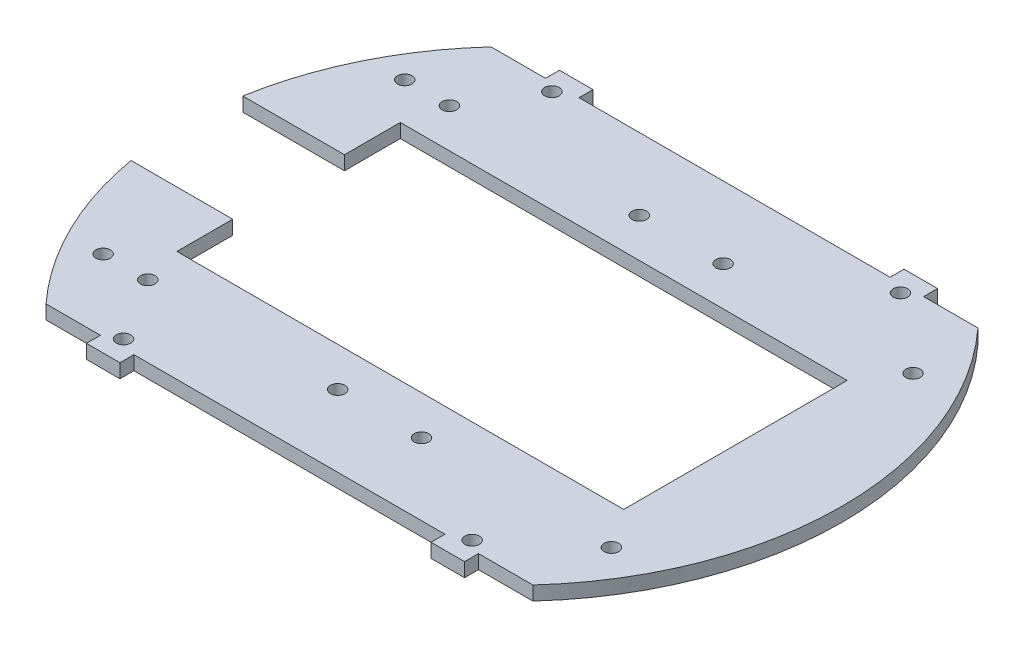
SolidWorks part; units mm, degrees
material "Acrylic (Medium-high impact)"
ref_plane "Front Plane" through (0, 0, 0) normal (0, 0, 1) x (1, 0, 0)
ref_plane "Top Plane" through (0, 0, 0) normal (0, 1, 0) x (1, 0, 0)
ref_plane "Right Plane" through (0, 0, 0) normal (1, 0, 0) x (0, 0, -1)
sketch "Sketch1" plane through (0, 0, 0) normal (0, 1, 0) x (1, 0, 0)
  line L0 (-73.9169, 12.7) -> (-73.9169, -12.7)
  line L1 (-35.3642, -50.6035) -> (-35.3642, -53.7785)
  line L2 (-55.356, -50.6035) -> (-42.9842, -50.6035)
  line L3 (-55.356, 50.6035) -> (-42.9842, 50.6035)
  line L4 (-48.5169, -34.29) -> (-48.5169, 34.29) construction
  line L5 (-48.5169, 34.29) -> (-5.3369, 34.29) construction
  line L6 (-5.3369, 34.29) -> (-5.3369, -34.29) construction
  line L7 (-5.3369, -34.29) -> (-48.5169, -34.29) construction
  line L8 (-73.9169, 0) -> (-48.5169, 0) construction
  line L9 (0, 50.6035) -> (0, -51.6195) construction
  line L10 (-73.9169, 12.7) -> (-73.9169, -12.7) construction
  line L11 (-50.8, 25.4) -> (50.8, 25.4)
  line L12 (-50.8, 25.4) -> (-50.8, -25.4)
  line L13 (-50.8, -25.4) -> (50.8, -25.4)
  line L14 (50.8, 25.4) -> (50.8, -25.4)
  line L15 (0, 0) -> (0, 25.4) construction
  line L16 (0, 0) -> (-50.8, 0) construction
  line L17 (13.7131, 34.29) -> (13.7131, -34.29) construction
  line L18 (13.7131, -34.29) -> (56.8931, -34.29) construction
  line L19 (56.8931, -34.29) -> (56.8931, 34.29) construction
  line L20 (56.8931, 34.29) -> (13.7131, 34.29) construction
  line L21 (39.6269, 48.6985) -> (39.6269, 50.6035) construction
  line L22 (39.6269, -48.6985) -> (39.6269, -50.6035) construction
  line L23 (-39.6269, -48.6985) -> (-39.6269, -50.6035) construction
  line L24 (-39.6269, 48.6985) -> (-39.6269, 50.6035) construction
  line L25 (39.6269, 48.6985) -> (41.2779, 48.6985) construction
  line L26 (39.6269, -48.6985) -> (41.2779, -48.6985) construction
  line L27 (-35.3642, -50.6035) -> (35.3642, -50.6035)
  line L28 (35.3642, -50.6035) -> (35.3642, -53.7785)
  line L29 (35.3642, -53.7785) -> (42.9842, -53.7785)
  line L30 (42.9842, -50.6035) -> (42.9842, -53.7785)
  line L31 (-35.3642, -53.7785) -> (-42.9842, -53.7785)
  line L32 (-42.9842, -50.6035) -> (-42.9842, -53.7785)
  line L33 (42.9842, 50.6035) -> (42.9842, 53.7785)
  line L34 (35.3642, 53.7785) -> (42.9842, 53.7785)
  line L35 (35.3642, 50.6035) -> (35.3642, 53.7785)
  line L36 (-35.3642, 50.6035) -> (-35.3642, 53.7785)
  line L37 (-35.3642, 53.7785) -> (-42.9842, 53.7785)
  line L38 (-42.9842, 50.6035) -> (-42.9842, 53.7785)
  line L39 (42.9842, -50.6035) -> (55.356, -50.6035)
  line L40 (42.9842, 50.6035) -> (55.356, 50.6035)
  line L41 (-35.3642, 50.6035) -> (35.3642, 50.6035)
  arc A0 (-73.9169, -12.7) -> (-55.356, -50.6035) centre (0, 0) ccw
  circle A1 centre (13.7131, 34.29) radius 1.651
  arc A2 (-55.356, 50.6035) -> (-73.9169, 12.7) centre (0, 0) ccw
  arc A3 (55.356, -50.6035) -> (55.356, 50.6035) centre (0, 0) ccw
  circle A4 centre (-58.6769, -34.29) radius 1.651
  circle A5 centre (-58.6769, 34.29) radius 1.651
  circle A6 centre (-39.6269, 48.6985) radius 1.651
  circle A7 centre (39.6269, 48.6985) radius 1.651
  circle A8 centre (-39.6269, -48.6985) radius 1.651
  circle A9 centre (39.6269, -48.6985) radius 1.651
  circle A10 centre (56.8931, 34.29) radius 1.651
  circle A11 centre (-58.6769, 34.29) radius 1.651 construction
  circle A12 centre (-48.5169, 34.29) radius 1.651
  circle A13 centre (-5.3369, 34.29) radius 1.651
  circle A14 centre (-5.3369, -34.29) radius 1.651
  circle A15 centre (-48.5169, -34.29) radius 1.651
  circle A16 centre (13.7131, -34.29) radius 1.651
  circle A17 centre (56.8931, -34.29) radius 1.651
  dimension "D3" = 3.302
  dimension "D1" = 43.18
  dimension "D2" = 68.58
  dimension "D4" = 25.4
  dimension "D5" = 101.6
  dimension "D6" = 50.8
  dimension "D7" = 19.05
  dimension "D10" = 19.05
extrude "Boss-Extrude1" add sketch "Sketch1" along normal blind 3.175
sketch "Sketch3" plane through (0, 3.175, 0) normal (0, 1, 0) x (1, 0, 0)
  line L0 (-50.8, 25.4) -> (-50.8, -25.4) construction
  line L1 (-73.9169, 12.7) -> (-50.8, 12.7)
  line L2 (-73.9169, 12.7) -> (-73.9169, -12.7)
  line L3 (-73.9169, -12.7) -> (-50.8, -12.7)
  line L4 (-50.8, 12.7) -> (-50.8, -12.7)
extrude "Cut-Extrude2" cut sketch "Sketch3" against normal up to surface (3.175 mm away) up to face at (56.8931, 0, 35.941)
